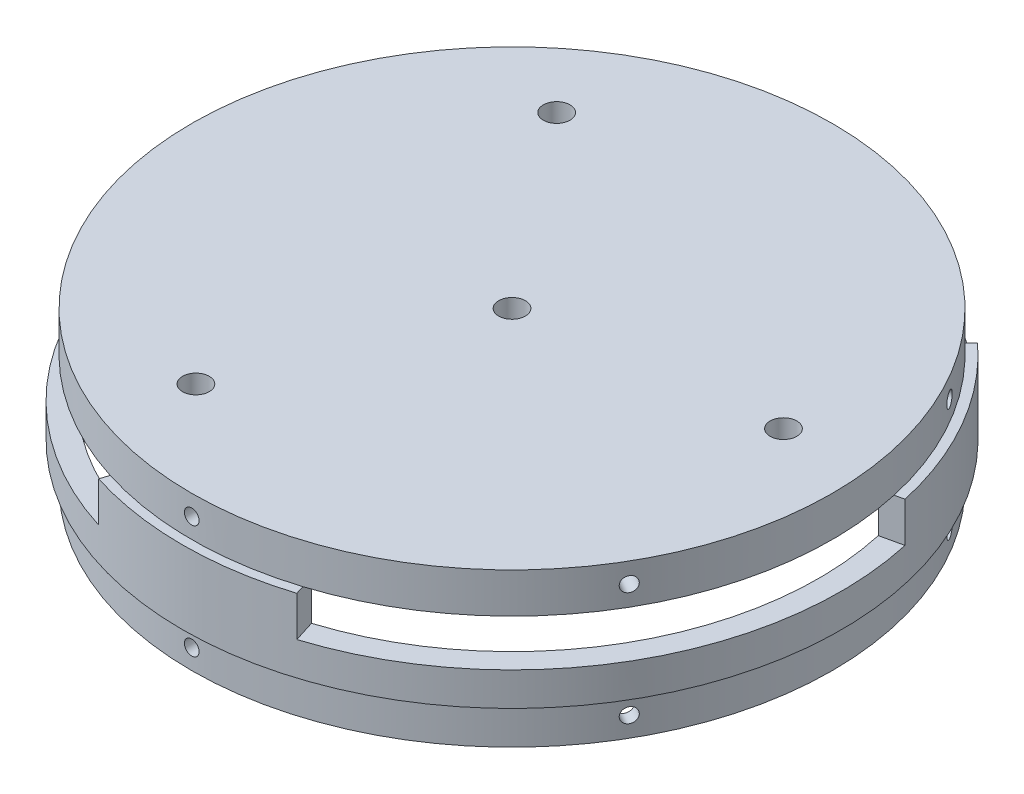
SolidWorks part; units mm, degrees
ref_plane "Front Plane" through (0, 0, 0) normal (0, 0, 1) x (1, 0, 0)
ref_plane "Top Plane" through (0, 0, 0) normal (0, 1, 0) x (1, 0, 0)
ref_plane "Right Plane" through (0, 0, 0) normal (1, 0, 0) x (0, 0, -1)
sketch "Sketch1" plane through (0, 0, 0) normal (0, 1, 0) x (1, 0, 0)
  line L0 (0, 0) -> (-52.9386, 57.7723)
  line L1 (0, 0) -> (52.9386, 57.7723)
  line L2 (0, 0) -> (0, 72.1431) construction
  circle A0 centre (0, 0) radius 78.359
  circle A1 centre (0, 0) radius 73.025
  circle A2 centre (0, 0) radius 76.1746
  dimension "D1" = 156.718
  dimension "D2" = 146.05
  dimension "D3" = 152.3492
  dimension "D4" = 85
extrude "Boss-Extrude1" add sketch "Sketch1" along normal blind 17.4625 contours L2 A2 L1 A0 | L2 A1 L1 A2 | L2 A2 L1 A1 | L2 A0 L1 A2 | A2 L2 A1 L0 | A0 L2 A2 L0 | A2 L2 A0 L0 | A1 L2 A2 L0 region at (-30.2233, 0, 68.6877) region at (-49.6224, 0, -55.7123) region at (-31.5151, 0, 71.6236) region at (-51.4031, 0, -57.6979)
ref_plane "Plane1" through (0, 8.7312, 0) normal (0, 1, 0) x (1, 0, 0)
extrude "Boss-Extrude2" add sketch "Sketch1<3>" along normal blind 9.525 from surface contours A2 L2 A1 L0 | L2 A2 L1 A1 | L2 A1 L1 A2 | A1 L2 A2 L0 region at (-30.2233, 0, 68.6877) region at (-49.6224, 0, -55.7123) starting at face at (0, 17.4625, 73.025)
sketch "Sketch1<3>" plane through (0, 0, 0) normal (0, 1, 0) x (1, 0, 0) same geometry as "Sketch1"
extrude "Boss-Extrude3" add sketch "Sketch1<4>" against normal blind 9.525 contours A2 L2 A1 L0 | A1 L2 A2 L0 | L2 A1 L1 A2 | L2 A2 L1 A1 region at (-30.2233, 0, 68.6877) region at (-49.6224, 0, -55.7123)
sketch "Sketch1<4>" plane through (0, 0, 0) normal (0, 1, 0) x (1, 0, 0) same geometry as "Sketch1"
ref_plane "Plane2" through (0, 0, -76.1746) normal (0, 0, -1) x (-1, 0, 0)
ref_plane "Plane5" through (0, 17.4625, 0) normal (0, 1, 0) x (1, 0, 0)
ref_axis "Axis1" through (0, 0, 0) along (0, 1, 0)
sketch "Sketch3" plane through (0, 0, -76.1746) normal (0, 0, -1) x (-1, 0, 0)
  line L0 (76.1746, 0) -> (-76.1746, 0) construction
  line L1 (-76.1746, -9.525) -> (76.1746, -9.525) construction
  line L2 (76.1746, 17.4625) -> (-76.1746, 17.4625) construction
  line L3 (76.1746, 26.9875) -> (-76.1746, 26.9875) construction
  line L4 (76.1746, 0) -> (-76.1746, 0)
  line L5 (-76.1746, -9.525) -> (76.1746, -9.525)
  line L6 (76.1746, 17.4625) -> (-76.1746, 17.4625)
  line L7 (76.1746, 26.9875) -> (-76.1746, 26.9875)
  line L8 (0, 26.9875) -> (0, 17.4625)
  line L9 (0, 0) -> (0, -9.525)
  circle A0 centre (0, 22.225) radius 1.75
  circle A1 centre (0, -4.7625) radius 1.75
  point P12 (0, 22.225)
  point P13 (0, -4.7625)
  point P14 (-77.5445, 179.1871)
  dimension "D1" = 3.5
extrude "Cut-Extrude2" cut sketch "Sketch3" against normal blind 9.525 contours L8 A0 | L8 A0 | L9 A1 | L9 A1 region at (-0.7427, 22.225, -76.1746) region at (0.7427, 22.225, -76.1746) region at (-0.7427, -4.7625, -76.1746) region at (0.7427, -4.7625, -76.1746)
extrude "Cut-Extrude3" cut sketch "Sketch1<7>" against normal blind 9.525 from surface contours L2 A1 L1 A2 | A1 L2 A2 L0 | A2 L2 A0 L0 | L2 A2 L1 A0 region at (-49.6224, 0, -55.7123) region at (-51.4031, 0, -57.6979) starting at plane "Plane5"
sketch "Sketch1<7>" plane through (0, 0, 0) normal (0, 1, 0) x (1, 0, 0) same geometry as "Sketch1"
pattern_circular "CirPattern2" count 3 over 360 about axis through (0, 0, 0) along (0, 1, 0) of "Cut-Extrude3"
ref_plane "Plane3" through (0, 26.9875, 0) normal (0, 1, 0) x (1, 0, 0)
sketch "Sketch4" plane through (0, 26.9875, 0) normal (0, 1, 0) x (1, 0, 0)
  circle A0 centre (0, 0) radius 73.025
  dimension "D1" = 146.05
extrude "Boss-Extrude4" add sketch "Sketch4" against normal blind 9.525
pattern_circular "CirPattern3" count 6 over 360 about axis through (0, 0, 0) along (0, 1, 0) of "Cut-Extrude2"
sketch "Sketch5" plane through (0, 26.9875, 0) normal (0, 1, 0) x (1, 0, 0)
  line L0 (0.0015, -0.0009) -> (-23.563, -74.7323) construction
  line L1 (0.0015, -0.0009) -> (-22.0157, -53.1519) construction
  circle A0 centre (0, 0) radius 3.175
  circle A1 centre (-22.0157, -53.1519) radius 3.175
  circle A2 centre (0, 0) radius 57.531 construction
  circle A3 centre (0.0015, 0.0009) radius 57.531 construction
  circle A4 centre (-35.0215, 45.643) radius 3.175
  circle A5 centre (0.0015, -0.0009) radius 57.531 construction
  circle A6 centre (57.0403, 7.5089) radius 3.175
  point P17 (0.001, 0)
  dimension "D1" = 6.35
  dimension "D3" = 6.35
  dimension "D2" = 57.531
  dimension "D5" = 5
extrude "Cut-Extrude4" cut sketch "Sketch5" against normal through all
equation "\"AB_Coupler_OD_Length\"= .6875in"
equation "\"AB_Coupling_Section_Length\"= 0.375in"
equation "\"AB_Coupler_Length\"= \"AB_Coupler_OD_Length\" + \"AB_Coupling_Section_Length\" * 2"
equation "\"D1@Boss-Extrude2\"=\"AB_Coupling_Section_Length\""
equation "\"D1@Boss-Extrude3\"=\"AB_Coupling_Section_Length\""
equation "\"D1@Boss-Extrude1\" = \"AB_Coupler_OD_Length\""
equation "\"Cutout_Angle\" = 85"
equation "\"AB_Coupler_Num_Screws\"= 6"
equation "\"Num_Cutouts\" = 3"
equation "\"D4@Sketch1\"=\"Cutout_Angle\""
equation "\"D1@CirPattern2\"=\"Num_Cutouts\""
equation "\"D1@CirPattern3\"=\"AB_Coupler_Num_Screws\""
equation "\"AB_Coupler_OD\"= 6.17in"
equation "\"AB_Coupler_ID\"= 5.75in"
equation "\"AB_Coupler_Surface_Diameter\"= 5.998in"
equation "\"D3@Sketch1\"=\"AB_Coupler_Surface_Diameter\""
equation "\"D2@Sketch1\"=\"AB_Coupler_ID\""
equation "\"D1@Sketch1\"=\"AB_Coupler_OD\""
equation "\"AB_Coupling_Screw_Diameter\"= 0.1065in"
equation "\"Aft_Section_Length\"= 40in"
equation "\"Aft_Lower_Length\"= 20in"
equation "\"Aft_Upper_Length\"= \"Aft_Section_Length\" - \"Aft_Lower_Length\" - \"AB_Coupler_OD_Length\""
equation "\"Mid_Coupler_Length\" = 10in"
equation "\"Lead_Screw_Dist\" = 2.25in"
equation "\"Lead_Screw_Diam\" = (27/64)*1in"
equation "\"Lead_Screw_Length\" = (\"Mid_Coupler_Length\" + 2*0.375in + 2*0.5in)"
equation "\"Bodytube_OD\" = 6.17in"
equation "\"Paddle_Pin_Offset\" = .25in"
equation "\"Bodytube_ID\" = 5.998in"
equation "\"Paddle_Pin_Radius\" = 2.55in"
equation "\"D1@Sketch4\"=\"AB_Coupler_ID\""
equation "\"D2@Sketch5\"=2.265"
